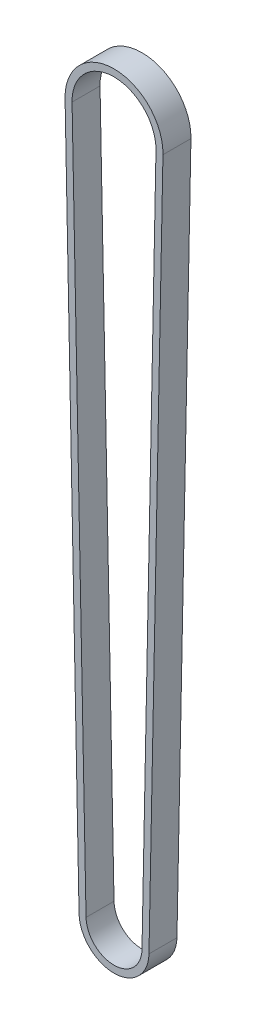
SolidWorks part; units mm, degrees
material "Rubber"
ref_plane "Front Plane" through (0, 0, 0) normal (0, 0, 1) x (1, 0, 0)
ref_plane "Top Plane" through (0, 0, 0) normal (0, 1, 0) x (1, 0, 0)
ref_plane "Right Plane" through (0, 0, 0) normal (1, 0, 0) x (0, 0, -1)
sketch "Sketch1" plane through (0, 0, 0) normal (0, 0, 1) x (1, 0, 0)
  line L0 (0, 0) -> (0, 400) construction
  line L1 (-15.9968, -0.32) -> (-23.9952, 399.52)
  line L2 (23.9952, 399.52) -> (15.9968, -0.32)
  line L3 (-19.996, -0.4) -> (-27.9944, 399.44)
  line L4 (27.9944, 399.44) -> (19.996, -0.4)
  arc A0 (-15.9968, -0.32) -> (15.9968, -0.32) centre (0, 0) ccw
  arc A1 (23.9952, 399.52) -> (-23.9952, 399.52) centre (0, 400) ccw
  arc A2 (27.9944, 399.44) -> (-27.9944, 399.44) centre (0, 400) ccw
  arc A3 (-19.996, -0.4) -> (19.996, -0.4) centre (0, 0) ccw
  dimension "D2" = 32
  dimension "D3" = 48
  dimension "D1" = 400
  dimension "D4" = 4
extrude "Boss-Extrude1" add sketch "Sketch1" along normal blind 16
ref_axis "Axis1" through (0, 400, 16) along (0, 0, -1)
ref_axis "Axis2" through (0, 0, 16) along (0, 0, -1)
ref_plane "Plane1" through (0, 0, 0) normal (1, 0, 0) x (0, 0, -1)
